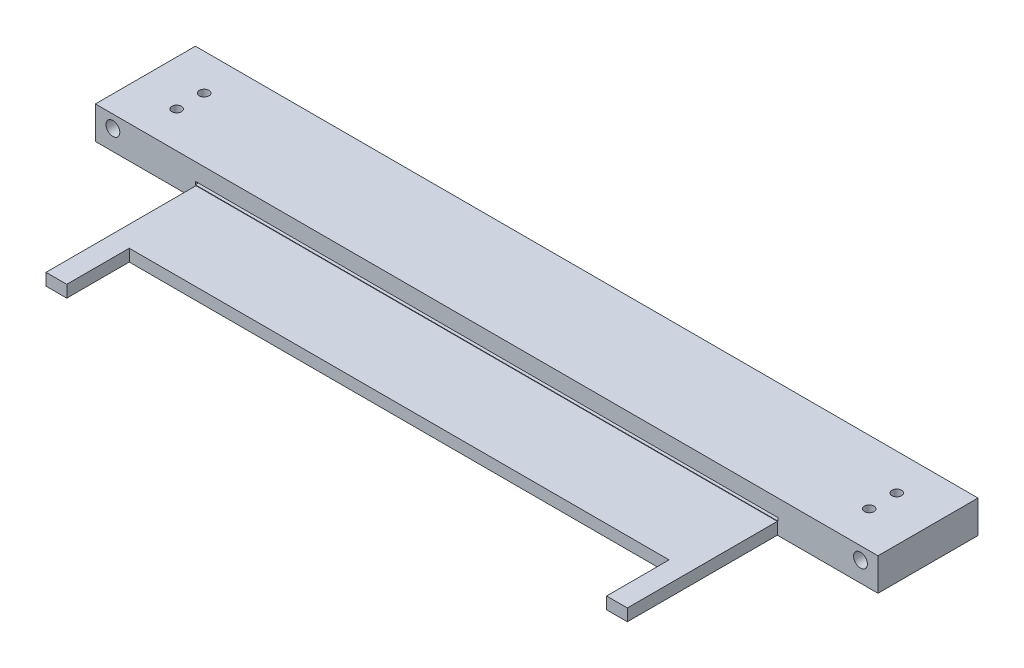
SolidWorks part; units mm, degrees
ref_plane "Front Plane" through (0, 0, 0) normal (0, 0, 1) x (1, 0, 0)
ref_plane "Top Plane" through (0, 0, 0) normal (0, 1, 0) x (1, 0, 0)
ref_plane "Right Plane" through (0, 0, 0) normal (1, 0, 0) x (0, 0, -1)
sketch "Sketch1" plane through (0, 0, 0) normal (1, 0, 0) x (0, 0, -1)
  line L1 (0, 0) -> (40, 0)
  line L2 (0, 0) -> (0, 10)
  line L3 (0, 10) -> (40, 10)
  line L4 (40, 0) -> (40, 10)
  dimension "D1" = 10
  dimension "D2" = 40
extrude "Boss-Extrude1" add sketch "Sketch1" along normal blind 312.998
sketch "Sketch2" plane through (0, 0, -40) normal (0, 0, -1) x (-1, 0, 0)
  line L1 (-272.994, 2) -> (-40.004, 2)
  line L2 (-272.994, 2) -> (-272.994, 3.2)
  line L3 (-272.994, 3.2) -> (-40.004, 3.2)
  line L4 (-40.004, 2) -> (-40.004, 3.2)
  line L5 (-272.994, 3.2) -> (-312.998, 0) construction
  line L6 (-40.004, 3.2) -> (0, 0) construction
  line L7 (-312.998, 0) -> (0, 0) construction
  dimension "D1" = 232.99
  dimension "D2" = 2
  dimension "D3" = 1.2
extrude "Cut-Extrude1" cut sketch "Sketch2" against normal through all
sketch "Sketch3" plane through (0, 10, 0) normal (0, 1, 0) x (1, 0, 0)
  line L0 (156.499, 71.4665) -> (156.499, -49.9307) construction
  line L1 (0, 40) -> (156.499, 71.4665) construction
  line L2 (156.499, 71.4665) -> (312.998, 40) construction
  line L3 (312.998, 40) -> (312.998, 0) construction
  line L4 (312.998, 40) -> (0, 40) construction
  line L5 (312.998, 40) -> (294.998, 25.5) construction
  line L6 (294.998, 25.5) -> (294.998, 14.5) construction
  line L7 (294.998, 14.5) -> (312.998, 0) construction
  circle A0 centre (294.998, 25.5) radius 1.9177
  circle A1 centre (294.998, 14.5) radius 1.9177
  circle A2 centre (18, 14.5) radius 1.9177
  circle A3 centre (18, 25.5) radius 1.9177
  dimension "D3" = 3.8354
  dimension "D1" = 18
  dimension "D2" = 14.5
extrude "Cut-Extrude2" cut sketch "Sketch3" against normal through all
sketch "Sketch4" plane through (0, 0, 0) normal (0, -1, 0) x (1, 0, 0)
  line L1 (14.5837, -12.5276) -> (14.5837, -16.4724)
  line L2 (14.5837, -16.4724) -> (18, -18.4448)
  line L3 (18, -18.4448) -> (21.4163, -16.4724)
  line L4 (21.4163, -16.4724) -> (21.4163, -12.5276)
  line L5 (21.4163, -12.5276) -> (18, -10.5552)
  line L6 (18, -10.5552) -> (14.5837, -12.5276)
  line L7 (14.5837, -23.5276) -> (14.5837, -27.4724)
  line L8 (14.5837, -27.4724) -> (18, -29.4448)
  line L9 (18, -29.4448) -> (21.4163, -27.4724)
  line L10 (21.4163, -27.4724) -> (21.4163, -23.5276)
  line L11 (21.4163, -23.5276) -> (18, -21.5552)
  line L12 (18, -21.5552) -> (14.5837, -23.5276)
  line L13 (298.4143, -12.5276) -> (294.998, -10.5552)
  line L14 (294.998, -10.5552) -> (291.5817, -12.5276)
  line L15 (291.5817, -12.5276) -> (291.5817, -16.4724)
  line L16 (291.5817, -16.4724) -> (294.998, -18.4448)
  line L17 (294.998, -18.4448) -> (298.4143, -16.4724)
  line L18 (298.4143, -16.4724) -> (298.4143, -12.5276)
  line L19 (291.5817, -23.5276) -> (291.5817, -27.4724)
  line L20 (291.5817, -27.4724) -> (294.998, -29.4448)
  line L21 (294.998, -29.4448) -> (298.4143, -27.4724)
  line L22 (298.4143, -27.4724) -> (298.4143, -23.5276)
  line L23 (298.4143, -23.5276) -> (294.998, -21.5552)
  line L24 (294.998, -21.5552) -> (291.5817, -23.5276)
  circle A0 centre (18, -14.5) radius 3.4163 construction
  circle A1 centre (18, -25.5) radius 3.4163 construction
  circle A2 centre (294.998, -14.5) radius 3.4163 construction
  circle A3 centre (294.998, -25.5) radius 3.4163 construction
  dimension "D1" = 6.8326
extrude "Cut-Extrude3" cut sketch "Sketch4" against normal blind 4.3
sketch "Sketch5" plane through (0, 0, 0) normal (0, 0, 1) x (1, 0, 0)
  line L0 (0, 10) -> (7, 5) construction
  line L1 (7, 5) -> (0, 0) construction
  line L2 (0, 10) -> (156.499, 87.0064) construction
  line L3 (156.499, 87.0064) -> (312.998, 10) construction
  line L4 (312.998, 10) -> (312.998, 0) construction
  line L5 (312.998, 10) -> (0, 10) construction
  line L6 (156.499, 87.0064) -> (156.499, -80.9825) construction
  line L7 (305.998, 5) -> (312.998, 0) construction
  line L8 (312.998, 10) -> (305.998, 5) construction
  circle A0 centre (7, 5) radius 2.7623
  circle A1 centre (305.998, 5) radius 2.7623
  dimension "D1" = 5.5245
  dimension "D2" = 7
extrude "Cut-Extrude4" cut sketch "Sketch5" against normal through all
sketch "Sketch6" plane through (0, 0, 0) normal (-1, 0, 0) x (0, 0, 1)
  line L0 (-40, 10) -> (-33, 8.4163) construction
  line L1 (-33, 8.4163) -> (-29.8453, 8.4163)
  line L2 (-33, 8.4163) -> (-33, 1.5837)
  line L3 (-33, 1.5837) -> (-29.8453, 1.5837)
  line L4 (-29.8453, 8.4163) -> (-29.8453, 1.5837)
  line L9 (-33, 1.5837) -> (-40, 0) construction
  line L10 (-40, 10) -> (-20, 18.9404) construction
  line L11 (-20, 18.9404) -> (0, 10) construction
  line L12 (-20, 18.9404) -> (-20, -7.3414) construction
  line L13 (-7, 1.5837) -> (0, 0) construction
  line L14 (0, 10) -> (-7, 8.4163) construction
  line L15 (-10.1547, 8.4163) -> (-10.1547, 1.5837)
  line L16 (-7, 1.5837) -> (-10.1547, 1.5837)
  line L17 (-7, 8.4163) -> (-7, 1.5837)
  line L18 (-7, 8.4163) -> (-10.1547, 8.4163)
  dimension "D1" = 7
  dimension "D2" = 3.1547
  dimension "D3" = 6.8326
extrude "Cut-Extrude5" cut sketch "Sketch6" against normal blind 15
ref_plane "Plane1" through (156.499, 0, 0) normal (-1, 0, 0) x (0, 0, 1)
sketch "Sketch7" plane through (0, 0, 0) normal (0, 0, 1) x (1, 0, 0)
  line L0 (312.998, 0) -> (0, 0) construction
  line L1 (40.249, 0) -> (272.749, 0)
  line L2 (40.249, 0) -> (40.249, 1.801)
  line L3 (40.249, 1.801) -> (272.749, 1.801)
  line L4 (272.749, 0) -> (272.749, 1.801)
  line L5 (40.249, 1.801) -> (40.004, 3.2) construction
  line L6 (272.994, 3.2) -> (272.749, 1.801) construction
  dimension "D1" = 232.5
extrude "Boss-Extrude2" add sketch "Sketch7" along normal blind 60
sketch "Sketch8" plane through (0, 1.801, 0) normal (0, 1, 0) x (1, 0, 0)
  line L0 (272.749, -60) -> (40.249, -60) construction
  line L1 (48.549, -35) -> (264.449, -35)
  line L2 (48.549, -35) -> (48.549, -60)
  line L3 (48.549, -60) -> (264.449, -60)
  line L4 (264.449, -35) -> (264.449, -60)
  line L5 (48.549, -35) -> (40.249, -60) construction
  line L6 (272.749, -60) -> (264.449, -35) construction
  dimension "D1" = 25
  dimension "D2" = 215.9
extrude "Cut-Extrude6" cut sketch "Sketch8" against normal up to next
sketch "Sketch9" plane through (0, 0, 0) normal (0, -1, 0) x (1, 0, 0)
  line L0 (0, -40) -> (0, 0)
  line L1 (0, 0) -> (40.249, 0)
  line L2 (40.249, 0) -> (40.249, 60)
  line L3 (40.249, 60) -> (48.549, 60)
  line L4 (48.549, 60) -> (48.549, 35)
  line L5 (48.549, 35) -> (264.449, 35)
  line L6 (264.449, 35) -> (264.449, 60)
  line L7 (264.449, 60) -> (272.749, 60)
  line L8 (272.749, 60) -> (272.749, 0)
  line L9 (272.749, 0) -> (312.998, 0)
  line L10 (312.998, 0) -> (312.998, -40)
  line L11 (312.998, -40) -> (0, -40)
  line L12 (21.4163, -16.4724) -> (21.4163, -12.5276) construction
  line L13 (17.9977, -10.5552) -> (14.5825, -12.5296)
  line L14 (14.5825, -12.5296) -> (14.5849, -16.4744)
  line L15 (14.5849, -16.4744) -> (18.0023, -18.4448)
  line L16 (18.0023, -18.4448) -> (21.4175, -16.4704)
  line L17 (21.4175, -16.4704) -> (21.4151, -12.5256)
  line L18 (21.4151, -12.5256) -> (17.9977, -10.5552)
  line L19 (18.0023, -21.5552) -> (14.5849, -23.5256)
  line L20 (14.5849, -23.5256) -> (14.5825, -27.4704)
  line L21 (14.5825, -27.4704) -> (17.9977, -29.4448)
  line L22 (17.9977, -29.4448) -> (21.4151, -27.4744)
  line L23 (21.4151, -27.4744) -> (21.4175, -23.5296)
  line L24 (21.4175, -23.5296) -> (18.0023, -21.5552)
  line L25 (295.0003, -10.5552) -> (291.5828, -12.5256)
  line L26 (291.5828, -12.5256) -> (291.5805, -16.4704)
  line L27 (291.5805, -16.4704) -> (294.9956, -18.4448)
  line L28 (294.9956, -18.4448) -> (298.4131, -16.4744)
  line L29 (298.4131, -16.4744) -> (298.4154, -12.5296)
  line L30 (298.4154, -12.5296) -> (295.0003, -10.5552)
  line L31 (294.9956, -21.5552) -> (291.5805, -23.5296)
  line L32 (291.5805, -23.5296) -> (291.5828, -27.4744)
  line L33 (291.5828, -27.4744) -> (295.0003, -29.4448)
  line L34 (295.0003, -29.4448) -> (298.4154, -27.4704)
  line L35 (298.4154, -27.4704) -> (298.4131, -23.5256)
  line L36 (298.4131, -23.5256) -> (294.9956, -21.5552)
  circle A0 centre (18, -14.5) radius 3.4163 construction
  circle A1 centre (18, -25.5) radius 3.4163 construction
  circle A2 centre (294.998, -14.5) radius 3.4163 construction
  circle A3 centre (294.998, -25.5) radius 3.4163 construction
  point P62 (17.9977, -14.5)
extrude "Boss-Extrude3" add sketch "Sketch9" along normal blind 3
